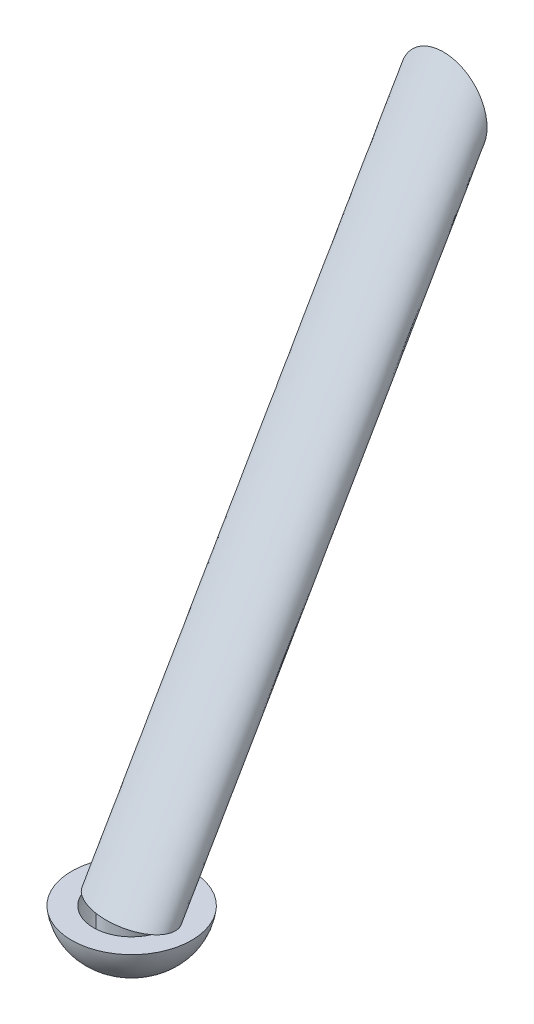
SolidWorks part; units mm, degrees
ref_plane "Front Plane" through (0, 0, 0) normal (0, 0, 1) x (1, 0, 0)
ref_plane "Top Plane" through (0, 0, 0) normal (0, 1, 0) x (1, 0, 0)
ref_plane "Right Plane" through (0, 0, 0) normal (1, 0, 0) x (0, 0, -1)
sketch "Sketch1" plane through (0, 0, 0) normal (1, 0, 0) x (0, 0, -1)
  line L0 (0, 0) -> (-1175.8461, -2036.6253)
  line L1 (0, 0) -> (0, -884.2253)
  line L2 (0, -884.2253) -> (-765.7615, -1326.3379)
  dimension "D1" = 30
  dimension "D2" = 1152.4
  dimension "D3" = 120
sketch "Sketch2" plane through (0, 0, 0) normal (0, 0, 1) x (1, 0, 0)
  circle A0 centre (0, 0) radius 152.4
  dimension "D1" = 304.8
sweep "Sweep2" add profiles "Sketch2" path "Sketch1"
sketch "Sketch5" plane through (0, 0, 1175.8461) normal (0, 0, 1) x (1, 0, 0)
  line L0 (0, 0) -> (0, -2036.6253) construction
  circle A0 centre (0, -2036.6253) radius 152.4 construction
  point P0 (0, -1884.2253)
ref_plane "Plane2" through (0, -1884.2253, 0) normal (0, 1, 0) x (1, 0, 0)
sketch "Sketch6" plane through (0, -1884.2253, 0) normal (0, 1, 0) x (1, 0, 0)
  circle A0 centre (0, -1175.8461) radius 415.386
extrude "Cut-Extrude2" cut sketch "Sketch6" against normal through all contours A0
sketch "Sketch7" plane through (0, 0, 0) normal (1, 0, 0) x (0, 0, -1)
  line L0 (0, 0) -> (-1175.8461, -2036.6253) construction
  line L1 (-1220.8876, -1884.2253) -> (-1297.0876, -1884.2253)
  line L2 (0, 0) -> (-1175.8461, -2036.6253) construction
  line L5 (-1087.858, -1884.2253) -> (-1087.858, -2036.6253)
  line L6 (-1175.8461, -1884.2253) -> (-1175.8461, -1975.6662)
  line L7 (-1175.8461, -1884.2253) -> (-1087.858, -1884.2253)
  arc A1 (-1175.8461, -1975.6662) -> (-1220.8876, -1884.2253) centre (-1119.521, -1891.1083) cw
  arc A2 (-1297.0876, -1884.2253) -> (-1087.858, -2036.6253) centre (-1120.6968, -1861.8842) ccw
  point P4 (-1087.858, -1884.2253)
  dimension "D1" = 152.4
  dimension "D2" = 101.6
  dimension "D4" = 177.8
  dimension "D3" = 76.2
revolve "Revolve1" add sketch "Sketch7" angle 360 about L5
sketch3d "3DSketch1"
  line L0 (-625, -785.072, -171.7385) -> (0, -1326.3379, 765.7615)
  line L2 (0, -884.2253, 0) -> (0, -1326.3379, 765.7615) construction
  point P0 (0, -1326.3379, 765.7615)
  point P2 (0, -884.2253, 0)
  point P5 (-625, -785.072, -171.7385)
  dimension "D2" = 625
  dimension "D1" = 30
ref_plane "Plane4" through (0, 0, -171.7385) normal (0, 0, 1) x (1, 0, 0)
sketch "Sketch22" plane through (0, 0, -171.7385) normal (0, 0, 1) x (1, 0, 0)
  circle A0 centre (-625, -785.072) radius 76.2
  dimension "D1" = 152.4
sweep "Sweep6" [suppressed] add profiles "Sketch22" path "3DSketch1"
mirror "Mirror2" [suppressed] about plane through (0, 0, 0) normal (1, 0, 0)
